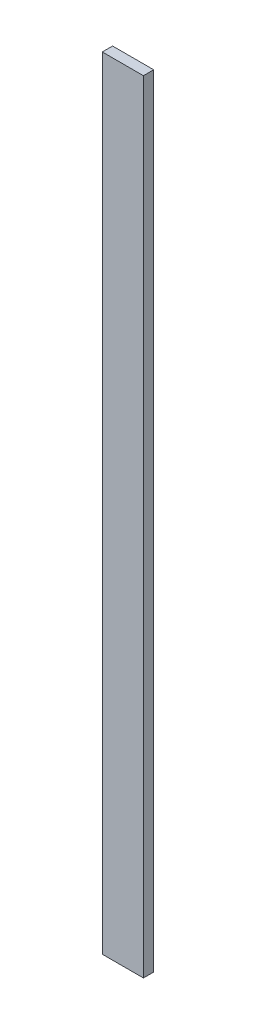
SolidWorks part; units mm, degrees
ref_plane "Front Plane" through (0, 0, 0) normal (0, 0, 1) x (1, 0, 0)
ref_plane "Top Plane" through (0, 0, 0) normal (0, 1, 0) x (1, 0, 0)
ref_plane "Right Plane" through (0, 0, 0) normal (1, 0, 0) x (0, 0, -1)
sketch "Sketch1" plane through (0, 0, 0) normal (0, 0, 1) x (1, 0, 0)
  line L1 (-12.7, -241.3) -> (-12.7, 241.3) construction
  line L2 (-12.7, 241.3) -> (12.7, 241.3)
  line L3 (-12.7, 241.3) -> (-12.7, -241.3)
  line L4 (-12.7, -241.3) -> (12.7, -241.3)
  line L5 (12.7, 241.3) -> (12.7, -241.3)
  point P6 (-12.7, 0)
  dimension "D1" = 482.6
  dimension "D2" = 25.4
  dimension "D3" = 12.7
  dimension "D4" = 241.3
extrude "Boss-Extrude1" add sketch "Sketch1" along normal mid plane 6.35
